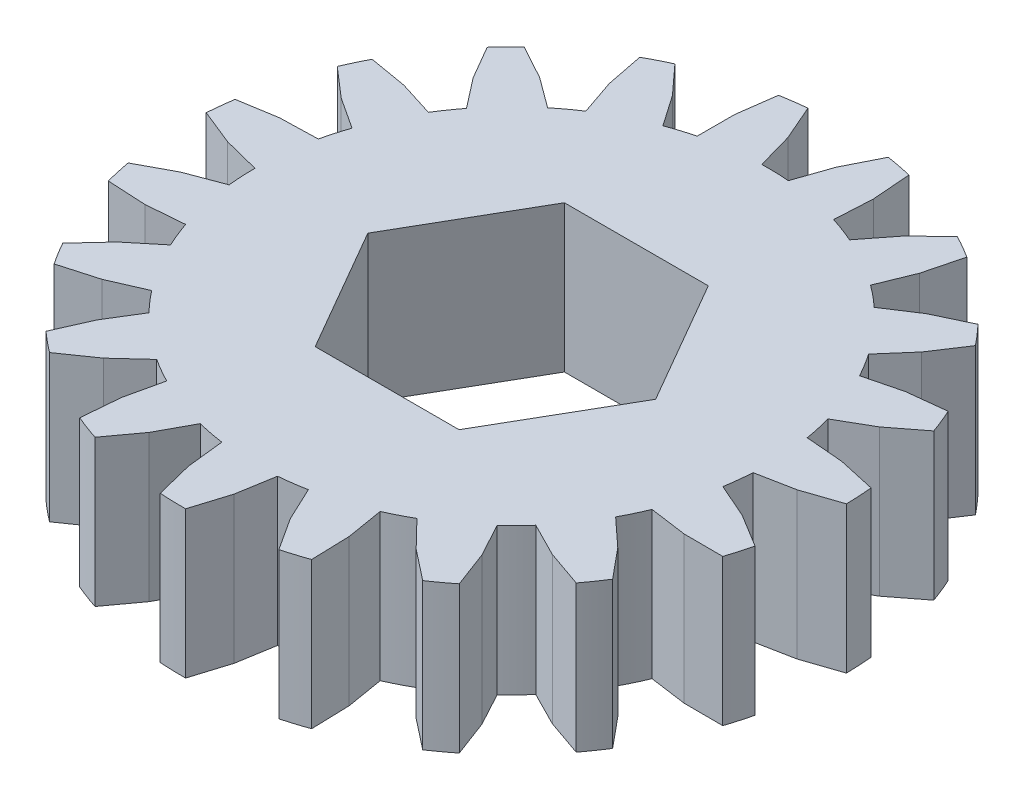
SolidWorks part; units mm, degrees
ref_plane "Front Plane" through (0, 0, 0) normal (0, 0, 1) x (1, 0, 0)
ref_plane "Top Plane" through (0, 0, 0) normal (0, 1, 0) x (1, 0, 0)
ref_plane "Right Plane" through (0, 0, 0) normal (1, 0, 0) x (0, 0, -1)
sketch "Sketch1" plane through (0, 0, 0) normal (0, 1, 0) x (1, 0, 0)
  line L1 (1.1319, 9.9357) -> (0.7133, 8.7209)
  line L2 (-0.1418, -5.0025) -> (1416.4972, 49974.9248) construction
  line L3 (-0.5673, 9.9839) -> (-0.2182, 8.7473)
  line L4 (-0.5673, 9.9839) -> (-1.0934, 11.1967)
  line L5 (4.2967, 9.0299) -> (3.5063, 8.0167)
  line L6 (1.1319, 9.9357) -> (1.7259, 11.1168)
  line L7 (2.7052, 9.6271) -> (2.6338, 8.3442)
  line L8 (2.7052, 9.6271) -> (2.6014, 10.9451)
  line L9 (4.2967, 9.0299) -> (5.242, 9.9541)
  line L10 (6.9959, 7.1455) -> (5.9194, 6.4439)
  line L11 (5.6846, 8.2271) -> (5.2005, 7.0369)
  line L12 (5.6846, 8.2271) -> (6.0143, 9.5074)
  line L13 (6.9959, 7.1455) -> (8.1901, 7.7127)
  line L14 (8.9369, 4.4868) -> (7.691, 4.1727)
  line L15 (8.0479, 5.9356) -> (7.2036, 4.967)
  line L16 (8.0479, 5.9356) -> (8.7755, 7.0394)
  line L17 (8.9369, 4.4868) -> (10.2506, 4.6355)
  line L18 (9.9096, 1.3419) -> (8.6291, 1.4493)
  line L19 (9.5391, 3.0008) -> (8.426, 2.3589)
  line L20 (9.5391, 3.0008) -> (10.5857, 3.8086)
  line L21 (9.9096, 1.3419) -> (11.2003, 1.056)
  line L22 (9.8083, -1.9485) -> (8.6322, -1.4311)
  line L23 (9.9966, -0.2591) -> (8.7354, -0.5049)
  line L24 (9.9966, -0.2591) -> (11.2488, 0.1651)
  line L25 (9.8083, -1.9485) -> (10.9363, -2.638)
  line L26 (8.6442, -5.0277) -> (7.6998, -4.1564)
  line L27 (9.3709, -3.491) -> (8.0982, -3.3139)
  line L28 (9.3709, -3.491) -> (10.6929, -3.4964)
  line L29 (8.6442, -5.0277) -> (9.4872, -6.0461)
  line L30 (6.5434, -7.562) -> (5.933, -6.4313)
  line L31 (7.7296, -6.3446) -> (6.5834, -5.7638)
  line L32 (7.7296, -6.3446) -> (8.9783, -6.7789)
  line L33 (6.5434, -7.562) -> (7.01, -8.799)
  line L34 (3.7334, -9.2769) -> (3.5233, -8.0093)
  line L35 (5.2507, -8.5106) -> (4.3552, -7.5891)
  line L36 (5.2507, -8.5106) -> (6.2907, -9.3268)
  line L37 (3.7334, -9.2769) -> (3.7732, -10.5984)
  line L38 (0.5189, -9.9865) -> (0.7318, -8.7193)
  line L39 (2.2028, -9.7544) -> (1.655, -8.5921)
  line L40 (2.2028, -9.7544) -> (2.9214, -10.8641)
  line L41 (0.5189, -9.9865) -> (0.1274, -11.2493)
  line L42 (-2.7518, -9.6139) -> (-2.139, -8.4845)
  line L43 (-1.0838, -9.9411) -> (-1.2245, -8.6639)
  line L44 (-1.0838, -9.9411) -> (-0.7644, -11.224)
  line L45 (-2.7518, -9.6139) -> (-3.5321, -10.6811)
  line L46 (-5.7243, -8.1995) -> (-4.778, -7.3303)
  line L47 (-4.2529, -9.0506) -> (-3.9713, -7.7969)
  line L48 (-4.2529, -9.0506) -> (-4.3674, -10.3676)
  line L49 (-5.7243, -8.1995) -> (-6.8089, -8.9555)
  line L50 (-8.0765, -5.8966) -> (-6.8993, -5.3817)
  line L51 (-6.9612, -7.1793) -> (-6.2878, -6.0849)
  line L52 (-6.9612, -7.1793) -> (-7.4972, -8.3878)
  line L53 (-8.0765, -5.8966) -> (-9.3478, -6.2595)
  line L54 (-9.5535, -2.9546) -> (-8.2729, -2.8499)
  line L55 (-8.9151, -4.53) -> (-7.9229, -3.7136)
  line L56 (-8.9151, -4.53) -> (-9.8145, -5.499)
  line L57 (-9.5535, -2.9546) -> (-10.8738, -2.8851)
  line L58 (-9.9953, 0.3075) -> (-8.75, -0.0093)
  line L59 (-9.903, -1.3898) -> (-8.6994, -0.9398)
  line L60 (-9.903, -1.3898) -> (-11.0682, -2.0143)
  line L61 (-9.9953, 0.3075) -> (-11.2214, 0.802)
  line L62 (-9.3539, 3.5363) -> (-8.2789, 2.8324)
  line L63 (-9.8176, 1.901) -> (-8.5332, 1.9358)
  line L64 (-9.8176, 1.901) -> (-11.1225, 1.6887)
  line L65 (-9.3539, 3.5363) -> (-10.353, 4.4021)
  line L66 (-7.6988, 6.3819) -> (-6.9107, 5.367)
  line L67 (-8.6684, 4.9858) -> (-7.4423, 4.6016)
  line L68 (-8.6684, 4.9858) -> (-9.9716, 5.2087)
  line L69 (-7.6988, 6.3819) -> (-8.3627, 7.5252)
  line L70 (-5.2095, 8.5359) -> (-4.7935, 7.3201)
  line L71 (-6.5799, 7.5303) -> (-5.5449, 6.7688)
  line L72 (-6.5799, 7.5303) -> (-7.74, 8.1642)
  line L73 (-5.2095, 8.5359) -> (-5.4661, 9.8328)
  line L74 (-2.1556, 9.7649) -> (-2.157, 8.48)
  line L75 (-3.7783, 9.2588) -> (-3.0466, 8.2025)
  line L76 (-3.7783, 9.2588) -> (-4.6697, 10.235)
  line L77 (-2.1556, 9.7649) -> (-1.9773, 11.0749)
  circle A0 centre (0, 0) radius 10 construction
  arc A1 (1.7259, 11.1168) -> (-1.0934, 11.1967) centre (0, 0) ccw
  arc A2 (0.7133, 8.7209) -> (-0.2182, 8.7473) centre (0, 0) ccw
  circle A3 centre (0, 0) radius 8.75 construction
  circle A5 centre (0, 0) radius 11.25 construction
  arc A6 (5.242, 9.9541) -> (2.6014, 10.9451) centre (0, 0) ccw
  arc A7 (3.5063, 8.0167) -> (2.6338, 8.3442) centre (0, 0) ccw
  arc A8 (8.1901, 7.7127) -> (6.0143, 9.5074) centre (0, 0) ccw
  arc A9 (5.9194, 6.4439) -> (5.2005, 7.0369) centre (0, 0) ccw
  arc A10 (10.2506, 4.6355) -> (8.7755, 7.0394) centre (0, 0) ccw
  arc A11 (7.691, 4.1727) -> (7.2036, 4.967) centre (0, 0) ccw
  arc A12 (11.2003, 1.056) -> (10.5857, 3.8086) centre (0, 0) ccw
  arc A13 (8.6291, 1.4493) -> (8.426, 2.3589) centre (0, 0) ccw
  arc A14 (10.9363, -2.638) -> (11.2488, 0.1651) centre (0, 0) ccw
  arc A15 (8.6322, -1.4311) -> (8.7354, -0.5049) centre (0, 0) ccw
  arc A16 (9.4872, -6.0461) -> (10.6929, -3.4964) centre (0, 0) ccw
  arc A17 (7.6998, -4.1564) -> (8.0982, -3.3139) centre (0, 0) ccw
  arc A18 (7.01, -8.799) -> (8.9783, -6.7789) centre (0, 0) ccw
  arc A19 (5.933, -6.4313) -> (6.5834, -5.7638) centre (0, 0) ccw
  arc A20 (3.7732, -10.5984) -> (6.2907, -9.3268) centre (0, 0) ccw
  arc A21 (3.5233, -8.0093) -> (4.3552, -7.5891) centre (0, 0) ccw
  arc A22 (0.1274, -11.2493) -> (2.9214, -10.8641) centre (0, 0) ccw
  arc A23 (0.7318, -8.7193) -> (1.655, -8.5921) centre (0, 0) ccw
  arc A24 (-3.5321, -10.6811) -> (-0.7644, -11.224) centre (0, 0) ccw
  arc A25 (-2.139, -8.4845) -> (-1.2245, -8.6639) centre (0, 0) ccw
  arc A26 (-6.8089, -8.9555) -> (-4.3674, -10.3676) centre (0, 0) ccw
  arc A27 (-4.778, -7.3303) -> (-3.9713, -7.7969) centre (0, 0) ccw
  arc A28 (-9.3478, -6.2595) -> (-7.4972, -8.3878) centre (0, 0) ccw
  arc A29 (-6.8993, -5.3817) -> (-6.2878, -6.0849) centre (0, 0) ccw
  arc A30 (-10.8738, -2.8851) -> (-9.8145, -5.499) centre (0, 0) ccw
  arc A31 (-8.2729, -2.8499) -> (-7.9229, -3.7136) centre (0, 0) ccw
  arc A32 (-11.2214, 0.802) -> (-11.0682, -2.0143) centre (0, 0) ccw
  arc A33 (-8.75, -0.0093) -> (-8.6994, -0.9398) centre (0, 0) ccw
  arc A34 (-10.353, 4.4021) -> (-11.1225, 1.6887) centre (0, 0) ccw
  arc A35 (-8.2789, 2.8324) -> (-8.5332, 1.9358) centre (0, 0) ccw
  arc A36 (-8.3627, 7.5252) -> (-9.9716, 5.2087) centre (0, 0) ccw
  arc A37 (-6.9107, 5.367) -> (-7.4423, 4.6016) centre (0, 0) ccw
  arc A38 (-5.4661, 9.8328) -> (-7.74, 8.1642) centre (0, 0) ccw
  arc A39 (-4.7935, 7.3201) -> (-5.5449, 6.7688) centre (0, 0) ccw
  arc A40 (-1.9773, 11.0749) -> (-4.6697, 10.235) centre (0, 0) ccw
  arc A41 (-2.157, 8.48) -> (-3.0466, 8.2025) centre (0, 0) ccw
  point P4 (0.3187, 11.2455)
  point P5 (0.2479, 8.7465)
  point P11 (-0.2182, 8.7473)
  point P12 (-0.5673, 9.9839)
  point P15 (-1.0934, 11.1967)
  point P21 (3.9529, 10.5327)
  point P22 (3.0745, 8.1921)
  point P26 (2.6338, 8.3442)
  point P27 (2.7052, 9.6271)
  point P28 (2.6014, 10.9451)
  point P34 (7.1587, 8.6785)
  point P35 (5.5678, 6.7499)
  point P37 (5.2005, 7.0369)
  point P38 (5.6846, 8.2271)
  point P39 (6.0143, 9.5074)
  point P45 (9.5887, 5.8839)
  point P46 (7.4579, 4.5763)
  point P48 (7.2036, 4.967)
  point P49 (8.0479, 5.9356)
  point P50 (8.7755, 7.0394)
  point P56 (10.9796, 2.4516)
  point P57 (8.5397, 1.9068)
  point P59 (8.426, 2.3589)
  point P60 (9.5391, 3.0008)
  point P61 (10.5857, 3.8086)
  point P67 (11.1808, -1.2463)
  point P68 (8.6961, -0.9693)
  point P70 (8.7354, -0.5049)
  point P71 (9.9966, -0.2591)
  point P72 (11.2488, 0.1651)
  point P78 (10.1703, -4.8092)
  point P79 (7.9102, -3.7405)
  point P81 (8.0982, -3.3139)
  point P82 (9.3709, -3.491)
  point P83 (10.6929, -3.4964)
  point P89 (8.0577, -7.8509)
  point P90 (6.2671, -6.1062)
  point P92 (6.5834, -5.7638)
  point P93 (7.7296, -6.3446)
  point P94 (8.9783, -6.7789)
  point P100 (5.0719, -10.0418)
  point P101 (3.9448, -7.8103)
  point P103 (4.3552, -7.5891)
  point P104 (5.2507, -8.5106)
  point P105 (6.2907, -9.3268)
  point P111 (1.5365, -11.1446)
  point P112 (1.1951, -8.668)
  point P114 (1.655, -8.5921)
  point P115 (2.2028, -9.7544)
  point P116 (2.9214, -10.8641)
  point P122 (-2.1653, -11.0396)
  point P123 (-1.6842, -8.5864)
  point P125 (-1.2245, -8.6639)
  point P126 (-1.0838, -9.9411)
  point P127 (-0.7644, -11.224)
  point P133 (-5.6326, -9.7384)
  point P134 (-4.3809, -7.5743)
  point P136 (-3.9713, -7.7969)
  point P137 (-4.2529, -9.0506)
  point P138 (-4.3674, -10.3676)
  point P144 (-8.4895, -7.3819)
  point P145 (-6.6029, -5.7414)
  point P147 (-6.2878, -6.0849)
  point P148 (-6.9612, -7.1793)
  point P149 (-7.4972, -8.3878)
  point P155 (-10.4264, -4.2254)
  point P156 (-8.1094, -3.2864)
  point P158 (-7.9229, -3.7136)
  point P159 (-8.9151, -4.53)
  point P160 (-9.8145, -5.499)
  point P166 (-11.2334, -0.611)
  point P167 (-8.7371, -0.4752)
  point P169 (-8.6994, -0.9398)
  point P170 (-9.903, -1.3898)
  point P171 (-11.0682, -2.0143)
  point P177 (-10.8231, 3.0696)
  point P178 (-8.418, 2.3875)
  point P180 (-8.5332, 1.9358)
  point P181 (-9.8176, 1.901)
  point P182 (-11.1225, 1.6887)
  point P188 (-9.24, 6.4175)
  point P189 (-7.1867, 4.9914)
  point P191 (-7.4423, 4.6016)
  point P192 (0, 0)
  point P193 (-8.6684, 4.9858)
  point P194 (-9.9716, 5.2087)
  point P200 (-6.6556, 9.07)
  point P201 (-5.1766, 7.0545)
  point P203 (-5.5449, 6.7688)
  point P204 (-6.5799, 7.5303)
  point P205 (-7.74, 8.1642)
  point P211 (-3.3499, 10.7397)
  point P212 (-2.6055, 8.3531)
  point P214 (-3.0466, 8.2025)
  point P215 (-3.7783, 9.2588)
  point P216 (-4.6697, 10.235)
  point P222 (0, 0)
  dimension "D1" = 1.25
  dimension "D3" = 20
  dimension "D2" = 1.25
  dimension "D4" = 2.8193
  dimension "D5" = 0.9316
  dimension "D6" = 19
sketch "Sketch3" plane through (0, 0, 0) normal (0, 1, 0) x (1, 0, 0)
  circle A0 centre (0, 0) radius 10 construction
  circle A1 centre (0, 0) radius 11.25
  dimension "D1" = 1.25
extrude "Boss-Extrude1" add sketch "Sketch3" along normal blind 2.5 and the other way blind 2.5
extrude "Cut-Extrude1" cut sketch "Sketch1" against normal through all and the other way through all
sketch "Sketch4" plane through (0, 2.5, 0) normal (0, 1, 0) x (1, 0, 0)
  line L1 (4.9075, 0) -> (2.4537, 4.25)
  line L2 (2.4537, 4.25) -> (-2.4537, 4.25)
  line L3 (-2.4537, 4.25) -> (-4.9075, 0)
  line L4 (-4.9075, 0) -> (-2.4537, -4.25)
  line L5 (-2.4537, -4.25) -> (2.4537, -4.25)
  line L6 (2.4537, -4.25) -> (4.9075, 0)
  circle A1 centre (0, 0) radius 4.25 construction
  dimension "D1" = 8.5
extrude "Cut-Extrude2" cut sketch "Sketch4" against normal through all
